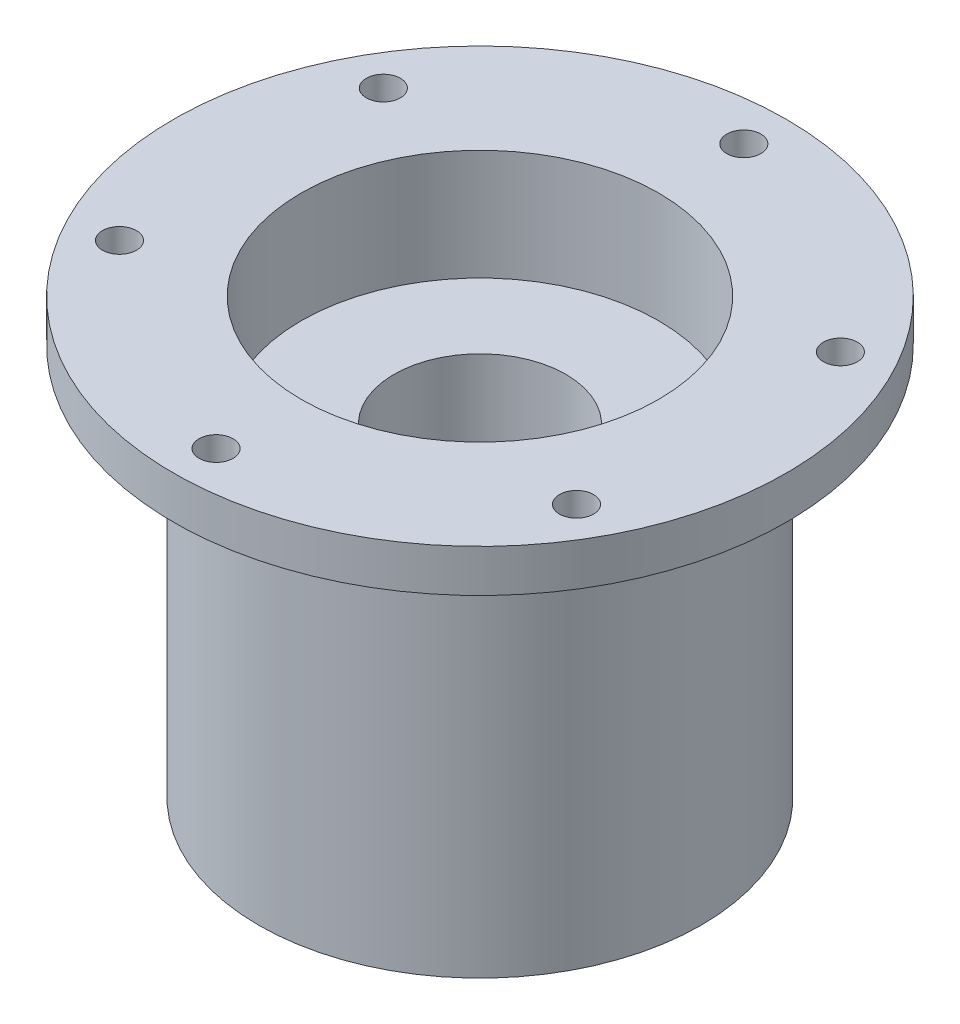
SolidWorks part; units mm, degrees
material "1060 Alloy"
ref_plane "Front Plane" through (0, 0, 0) normal (0, 0, 1) x (1, 0, 0)
ref_plane "Top Plane" through (0, 0, 0) normal (0, 1, 0) x (1, 0, 0)
ref_plane "Right Plane" through (0, 0, 0) normal (1, 0, 0) x (0, 0, -1)
sketch "Sketch1" plane through (0, 0, 0) normal (0, 0, 1) x (1, 0, 0)
  line L1 (21, 25.5) -> (21, 12.5)
  line L2 (21, 12.5) -> (10.1, 12.5)
  line L3 (10.1, 12.5) -> (10.1, -12.5)
  line L4 (26, 20.5) -> (26, -25.5)
  line L5 (26, -25.5) -> (21, -25.5)
  line L6 (21, -25.5) -> (21, -12.5)
  line L7 (21, -12.5) -> (10.1, -12.5)
  line L8 (0, 0) -> (0, 21.563) construction
  line L10 (36, 25.5) -> (36, 20.5)
  line L11 (36, 20.5) -> (26, 20.5)
  line L13 (21, 25.5) -> (36, 25.5)
  point P11 (10.1, 0)
  dimension "D1" = 13
  dimension "D2" = 13
  dimension "D3" = 21
  dimension "D4" = 10.1
  dimension "D5" = 25
  dimension "D6" = 5
  dimension "D7" = 10
  dimension "D8" = 5
revolve "Revolve1" add sketch "Sketch1" angle 360 about L8
sketch "Sketch2" plane through (0, 20.5, 0) normal (0, -1, 0) x (1, 0, 0)
  circle A0 centre (0, 0) radius 31 construction
  circle A1 centre (0, 31) radius 2
  circle A2 centre (26.8468, 15.5) radius 2
  circle A3 centre (26.8468, -15.5) radius 2
  circle A4 centre (0, -31) radius 2
  circle A5 centre (-26.8468, -15.5) radius 2
  circle A6 centre (-26.8468, 15.5) radius 2
  point P17 (0, 0)
  dimension "D1" = 62
  dimension "D2" = 4
  dimension "D3" = 6
extrude "Cut-Extrude1" cut sketch "Sketch2" against normal blind 10
fillet "Fillet1" radius 2 1 edges at (0, 20.5, -26)
